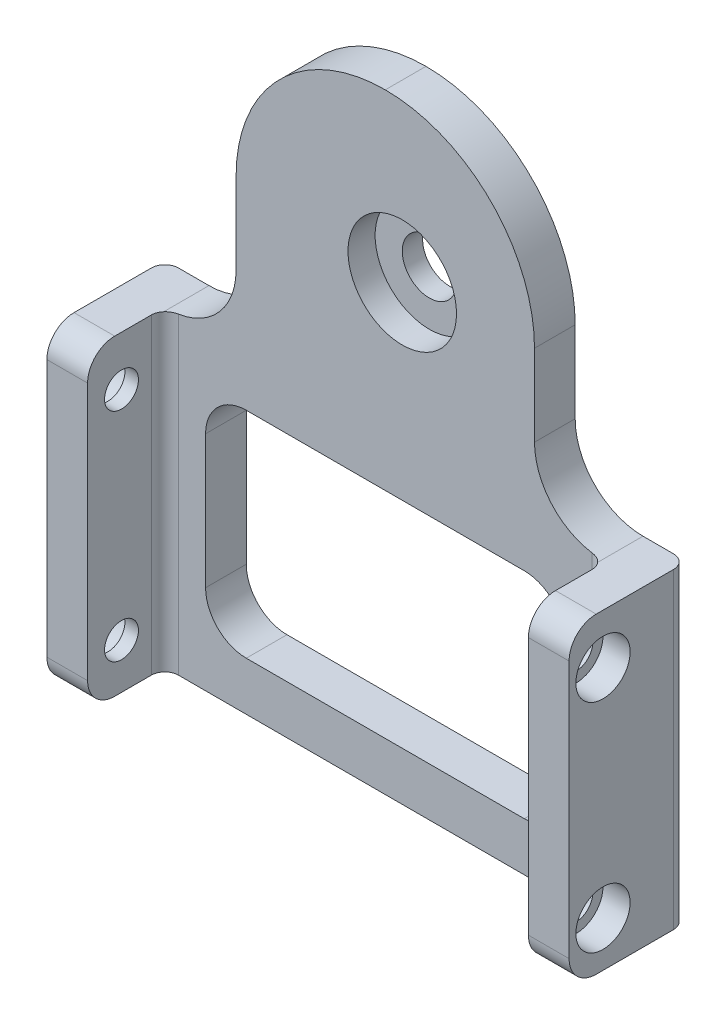
SolidWorks part; units mm, degrees
ref_plane "Front Plane" through (0, 0, 0) normal (0, 0, 1) x (1, 0, 0)
ref_plane "Top Plane" through (0, 0, 0) normal (0, 1, 0) x (1, 0, 0)
ref_plane "Right Plane" through (0, 0, 0) normal (1, 0, 0) x (0, 0, -1)
sketch "Sketch1" plane through (0, 0, 0) normal (0, 0, 1) x (1, 0, 0)
  line L0 (-11, 11.5) -> (-19.25, 11.5)
  line L1 (19.25, 11.5) -> (11, 11.5)
  line L2 (19.25, 11.5) -> (19.25, -11.5)
  line L3 (19.25, -11.5) -> (-19.25, -11.5)
  line L4 (-19.25, 11.5) -> (-19.25, -11.5)
  line L5 (19.25, 11.5) -> (-19.25, -11.5) construction
  line L6 (19.25, -11.5) -> (-19.25, 11.5) construction
  line L7 (-19.25, 11.5) -> (-16.25, 11.5)
  line L8 (-19.25, 11.5) -> (-19.25, -11.5)
  line L9 (-19.25, -11.5) -> (-16.25, -11.5)
  line L10 (-16.25, 11.5) -> (-16.25, -11.5)
  line L11 (19.25, 11.5) -> (16.25, 11.5)
  line L12 (19.25, 11.5) -> (19.25, -11.5)
  line L13 (19.25, -11.5) -> (16.25, -11.5)
  line L14 (16.25, 11.5) -> (16.25, -11.5)
  line L16 (-11, 11.5) -> (-11, 33.5)
  line L17 (-11, 33.5) -> (11, 33.5)
  line L18 (11, 11.5) -> (11, 33.5)
  line L20 (-13.25, 7.9156) -> (13.25, 7.9156)
  line L21 (-13.25, 7.9156) -> (-13.25, -7.9156)
  line L22 (-13.25, -7.9156) -> (13.25, -7.9156)
  line L23 (13.25, 7.9156) -> (13.25, -7.9156)
  line L24 (-13.25, 7.9156) -> (13.25, -7.9156) construction
  line L25 (-13.25, -7.9156) -> (13.25, 7.9156) construction
  circle A0 centre (1.25, 21.83) radius 2
  point P0 (0, 0)
  point P15 (0, 33.5)
  point P18 (0, 0)
  dimension "D10" = 4
  dimension "D7" = 12.25
  dimension "D1" = 32.5
  dimension "D2" = 3
  dimension "D3" = 3
  dimension "D4" = 22
  dimension "D5" = 23
  dimension "D6" = 10.33
  dimension "D8" = 6
extrude "Boss-Extrude1" add sketch "Sketch1" along normal blind 3 contours L1 L18 L17 L16 L0 L10 L3 L14 A0 region at (-0.0196, 13.2794, 0)
extrude "Boss-Extrude2" add sketch "Sketch1<4>" along normal blind 8.7 contours L1 L14 L3 L2 | L10 L0 L4 L3 region at (-17.75, 0, 0) region at (17.75, 0, 0)
sketch "Sketch1<4>" plane through (0, 0, 0) normal (0, 0, 1) x (1, 0, 0) same geometry as "Sketch1"
sketch "Sketch2" plane through (19.25, 0, 0) normal (1, 0, 0) x (0, 0, -1)
  line L0 (-8.7, 11.5) -> (0, 11.5) construction
  line L1 (-8.7, 11.5) -> (-8.7, -11.5) construction
  circle A0 centre (-6.2, 7.84) radius 1.25
  circle A1 centre (-6.2, -8.16) radius 1.25
  dimension "D1" = 2.5
  dimension "D2" = 3.66
  dimension "D3" = 2.5
  dimension "D4" = 16
extrude "Cut-Extrude1" cut sketch "Sketch2" against normal up to surface (38.5 mm away) up to face at (-19.25, 0, 4.35)
sketch "Sketch3" plane through (0, 0, 0) normal (0, 0, -1) x (-1, 0, 0)
  circle A0 centre (-1.25, 21.83) radius 2.5
  circle A1 centre (-1.25, 21.83) radius 2 construction
  circle M2 centre (-1.25, 21.83) radius 2
  dimension "D1" = 0.5
extrude "Boss-Extrude4" add sketch "Sketch3" along normal blind 0.5 contours A0 M2 region at (3.6793, 21.83, 0)
fillet "Fillet1" radius 11 2 edges at (-11, 33.5, 1.5) (11, 33.5, 1.5)
fillet "Fillet2" radius 3 4 edges at (-13.25, 7.9156, 1.5) (-13.25, -7.9156, 1.5) (13.25, -7.9156, 1.5) (13.25, 7.9156, 1.5)
sketch "Sketch4" plane through (-19.25, 0, 0) normal (-1, 0, 0) x (0, 0, 1)
  circle A0 centre (6.2, 7.84) radius 2
  circle A1 centre (6.2, -8.16) radius 2
  dimension "D1" = 4
extrude "Cut-Extrude2" cut sketch "Sketch4" against normal blind 2
mirror "Mirror1" about plane through (0, 0, 0) normal (1, 0, 0) of "Cut-Extrude2"
fillet "Fillet3" radius 2 4 edges at (17.75, 11.5, 8.7) (17.75, -11.5, 8.7) (-17.75, -11.5, 8.7) (-17.75, 11.5, 8.7)
fillet "Fillet4" radius 1 4 edges at (19.25, 0, 0) (-19.25, 0, 0) (-16.25, 0, 3) (16.25, 0, 3)
fillet "Fillet5" radius 5 2 edges at (-11, 11.5, 1.5) (11, 11.5, 1.5)
sketch "Sketch5" plane through (0, 0, 3) normal (0, 0, 1) x (1, 0, 0)
  circle A0 centre (1.25, 21.83) radius 4
  dimension "D1" = 8
extrude "Cut-Extrude3" cut sketch "Sketch5" against normal offset from surface (2 mm away) 1 up to face at (3.75, 21.83, 0)
move or copy body "Corpo-Mover/Copiar1" [suppressed] bodies to move or copy 108
